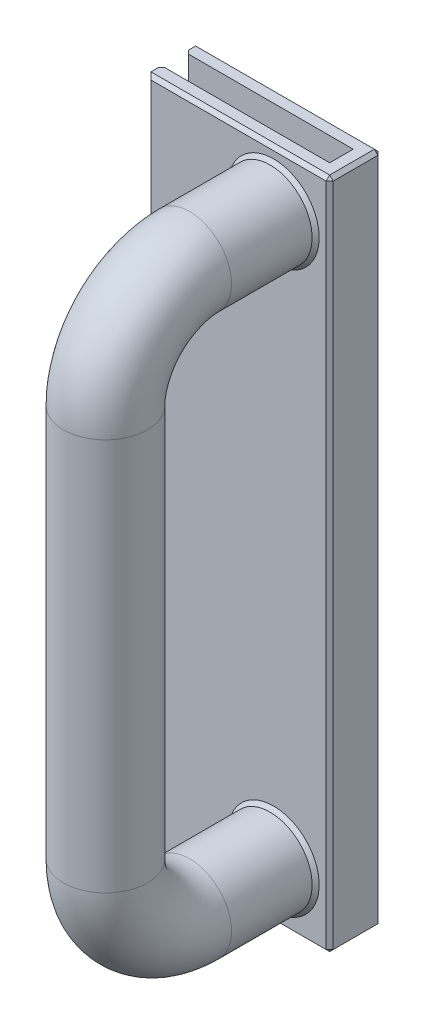
SolidWorks part; units mm, degrees
ref_plane "Front Plane" through (0, 0, 0) normal (0, 0, 1) x (1, 0, 0)
ref_plane "Top Plane" through (0, 0, 0) normal (0, 1, 0) x (1, 0, 0)
ref_plane "Right Plane" through (0, 0, 0) normal (1, 0, 0) x (0, 0, -1)
sketch "Sketch1" plane through (0, 0, 0) normal (0, 1, 0) x (1, 0, 0)
  line L0 (-19.05, 2.667) -> (19.05, 2.667)
  line L1 (-19.05, -2.667) -> (19.05, -2.667) construction
  line L2 (-19.05, -2.667) -> (-19.05, 2.667) construction
  line L3 (-19.05, 2.667) -> (19.05, 2.667) construction
  line L4 (19.05, -2.667) -> (19.05, 2.667) construction
  line L5 (-19.05, -2.667) -> (19.05, 2.667) construction
  line L6 (-19.05, 2.667) -> (19.05, -2.667) construction
  line L7 (19.05, 2.667) -> (19.05, -2.667)
  line L8 (19.05, -2.667) -> (-19.05, -2.667)
  line L9 (-19.05, -2.667) -> (-19.05, -5.867)
  line L10 (-19.05, -5.867) -> (22.25, -5.867)
  line L11 (22.25, -5.867) -> (22.25, 5.867)
  line L12 (22.25, 5.867) -> (-19.05, 5.867)
  line L13 (-19.05, 5.867) -> (-19.05, 2.667)
  point P0 (0, 0)
  dimension "D1" = 5.334
  dimension "D2" = 38.1
  dimension "D4" = 3.2
extrude "Boss-Extrude1" add sketch "Sketch1" along normal blind 152.4 contours L0 L7 L8 L9 L10 L11 L12 L13
sketch "Sketch2" plane through (0, 0, 5.867) normal (0, 0, 1) x (1, 0, 0)
  line L6 (-19.05, 0) -> (22.25, 0) construction
  line L7 (22.25, 152.4) -> (22.25, 0) construction
  circle A4 centre (9.55, 12.7) radius 9.525
  dimension "D1" = 19.05
  dimension "D2" = 3.175
sketch3d "3DSketch1"
  line L0 (9.55, 12.7, 5.867) -> (9.55, 12.7, 24.917)
  line L1 (9.55, 31.75, 43.967) -> (9.55, 120.65, 43.967)
  line L2 (9.55, 139.7, 24.917) -> (9.55, 139.7, 5.867)
  line L3 (9.55, 12.7, 5.867) -> (9.55, 0, 5.867) construction
  line L4 (-19.05, 0, 5.867) -> (22.25, 0, 5.867) construction
  line L5 (9.55, 139.7, 5.867) -> (9.55, 152.4, 5.867) construction
  line L6 (-19.05, 152.4, 5.867) -> (22.25, 152.4, 5.867) construction
  arc A0 (9.55, 12.7, 24.917) -> (9.55, 31.75, 43.967) centre (9.55, 31.75, 24.917) cw
  arc A1 (9.55, 120.65, 43.967) -> (9.55, 139.7, 24.917) centre (9.55, 120.65, 24.917) cw
  point P4 (-9.5, 31.75, 24.917)
  point P7 (-9.5, 120.65, 24.917)
  dimension "D2" = 38.1
  dimension "D1" = 19.05
sweep "Sweep1" add profiles "Sketch2" path "3DSketch1"
chamfer "Chamfer1" distance 0.8 angle 45 14 edges at (-19.05, 76.2, -2.667) (-19.05, 76.2, 2.667) (1.6, 0, -5.867) (22.25, 0, 0) (1.6, 0, 5.867) (22.25, 76.2, -5.867) (22.25, 76.2, 5.867) (-19.05, 76.2, -5.867) (1.6, 152.4, -5.867) (22.25, 152.4, 0) (1.6, 152.4, 5.867) (-19.05, 76.2, 5.867) (19.075, 12.7, 5.867) (19.075, 139.7, 5.867)
mirror "Mirror3" [suppressed] about plane through (0, 0, 0) normal (1, 0, 0) of bodies 102
delete or keep bodies "Body-Delete/Keep 1" [suppressed] type delete bodies bodies 102
equation "\"w\"= 0.4mm"
equation "\"D3@Sketch1\"=8*\"w\""
equation "\"D4@Sketch1\"=8*\"w\""
equation "\"panel\"= .220in'thickness of the polycarb"
equation "\"panel-interference\"= .01in'magnitude of the interference fit"
equation "\"slot-width\"= \"panel\" - \"panel-interference\""
equation "\"D1@Sketch1\"=\"slot-width\""
equation "\"handle_dia\"= .75in"
equation "\"handle_height\"= 6in"
equation "\"handle_depth\"= 1.5in"
equation "\"D1@Sketch2\"=\"handle_dia\""
equation "\"D2@3DSketch1\"=\"handle_depth\""
equation "\"D1@3DSketch1\"=\"handle_dia\""
equation "\"D1@Boss-Extrude1\"=\"handle_height\""
equation "\"iface_depth\"= 1.5in"
equation "\"D2@Sketch1\"=\"iface_depth\""
